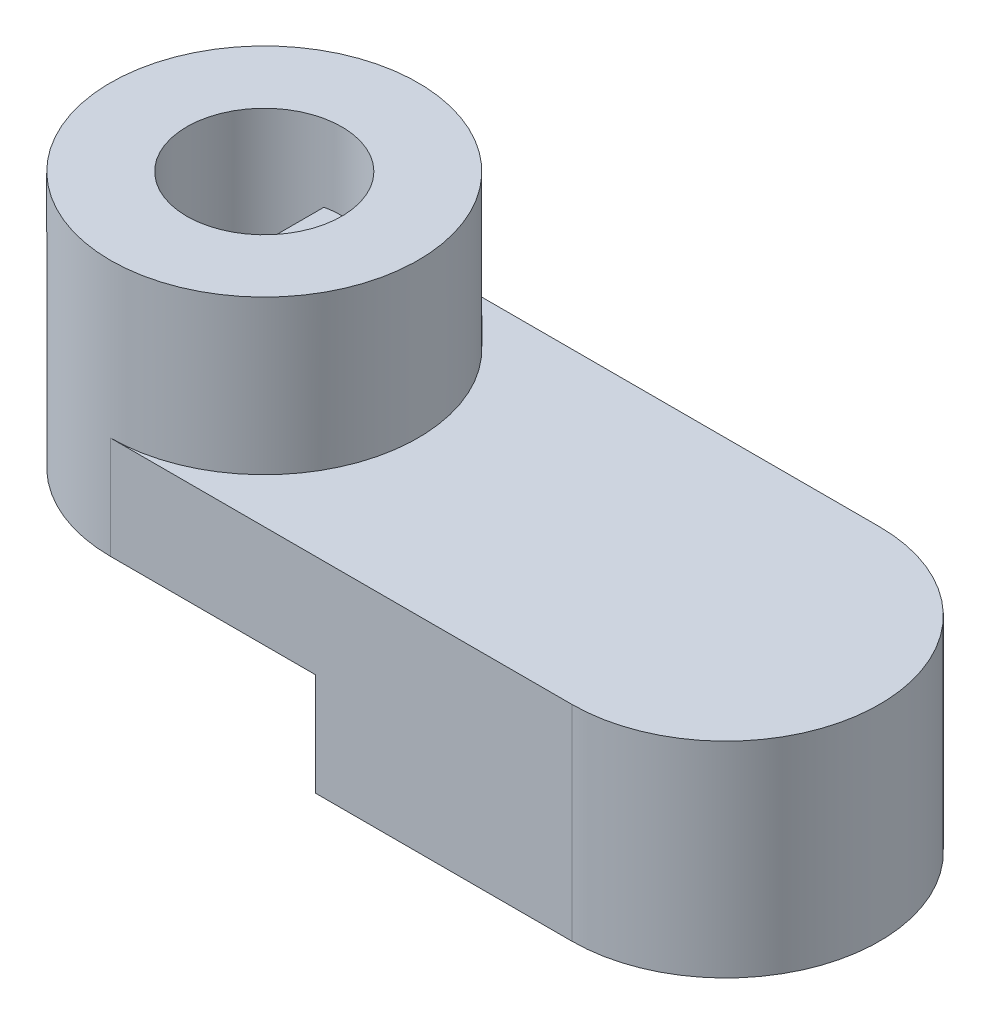
SolidWorks part; units mm, degrees
ref_plane "Front" through (0, 0, 0) normal (0, 0, 1) x (1, 0, 0)
ref_plane "Top" through (0, 0, 0) normal (0, 1, 0) x (1, 0, 0)
ref_plane "Right" through (0, 0, 0) normal (1, 0, 0) x (0, 0, -1)
sketch "Sketch1" plane through (0, 0, 0) normal (0, 0, 1) x (1, 0, 0)
  line L8 (0, 0) -> (-12.7, 0)
  line L11 (-23.8125, 3.175) -> (-23.8125, 6.35)
  line L12 (-23.8125, 6.35) -> (0, 6.35)
  line L15 (0, 6.35) -> (0, 0)
  line L16 (-12.7, 0) -> (-12.7, 3.175)
  line L17 (-12.7, 3.175) -> (-23.8125, 3.175)
  point P1 (0, 6.0818)
  point P2 (0, 0)
  dimension "D1" = 3.175
  dimension "D2" = 23.8125
  dimension "D3" = 12.7
extrude "Boss-Extrude1" add sketch "Sketch1" along normal mid plane 9.525
sketch "Sketch3" plane through (0, 0, 0) normal (0, -1, 0) x (1, 0, 0)
  line L0 (-12.7, 4.7625) -> (0, 4.7625) construction
  line L1 (-23.8125, 4.7625) -> (-23.8125, -4.7625) construction
  line L2 (-23.8125, 0) -> (-23.8125, 4.7625)
  line L3 (-23.8125, 4.7625) -> (-19.05, 4.7625)
  line L4 (-19.05, -4.7625) -> (-23.8125, -4.7625)
  line L5 (-23.8125, -4.7625) -> (-23.8125, 0)
  line L6 (0, 4.7625) -> (0, -4.7625) construction
  line L7 (-12.7, 4.7625) -> (0, 4.7625) construction
  line L8 (-12.7, -4.7625) -> (0, -4.7625) construction
  line L9 (-4.7625, 4.7625) -> (0, 4.7625)
  line L10 (0, 4.7625) -> (0, 0)
  line L11 (0, 0) -> (0, -4.7625)
  line L12 (0, -4.7625) -> (-4.7625, -4.7625)
  arc A0 (-19.05, 4.7625) -> (-19.05, -4.7625) centre (-19.05, 0) ccw
  arc A1 (-4.7625, -4.7625) -> (-4.7625, 4.7625) centre (-4.7625, 0) ccw
  line M2 (-12.7, -4.7625) -> (0, -4.7625)
  line M3 (0, -4.7625) -> (0, 4.7625)
  line M4 (0, 4.7625) -> (-12.7, 4.7625)
extrude "Cut-Extrude2" cut sketch "Sketch3" against normal up to next contours A0 M4 | A0 M2 | A1 M3 M4 | A1 M2 M3 region at (-22.7487, 0, -3.6987) region at (-22.7487, 0, 3.6987) region at (-1.0638, 0, -3.6987) region at (-1.0638, 0, 3.6987)
sketch "Sketch5" plane through (0, 6.35, 0) normal (0, 1, 0) x (1, 0, 0)
  circle A0 centre (-19.05, 0) radius 4.7625
  arc A1 (-19.05, 4.7625) -> (-19.05, -4.7625) centre (-19.05, 0) ccw construction
  circle A2 centre (-19.05, 0) radius 2.4
  dimension "D1" = 4.8
extrude "Boss-Extrude2" add sketch "Sketch5" along normal blind 4.7625
sketch "Sketch6" plane through (0, 6.35, 0) normal (0, 1, 0) x (1, 0, 0)
  line L0 (-19.55, -2.3473) -> (-19.55, 2.3473)
  line L5 (-18.55, -2.3473) -> (-18.55, 2.3473)
  line L6 (-18.55, 0) -> (-19.55, 0) construction
  circle A1 centre (-19.05, 0) radius 2.4 construction
  arc A2 (-18.55, 2.3473) -> (-19.55, 2.3473) centre (-19.05, 0) ccw
  arc A3 (-19.55, -2.3473) -> (-18.55, -2.3473) centre (-19.05, 0) ccw
  dimension "D1" = 1
extrude "Boss-Extrude3" add sketch "Sketch6" along normal blind 2.3813
